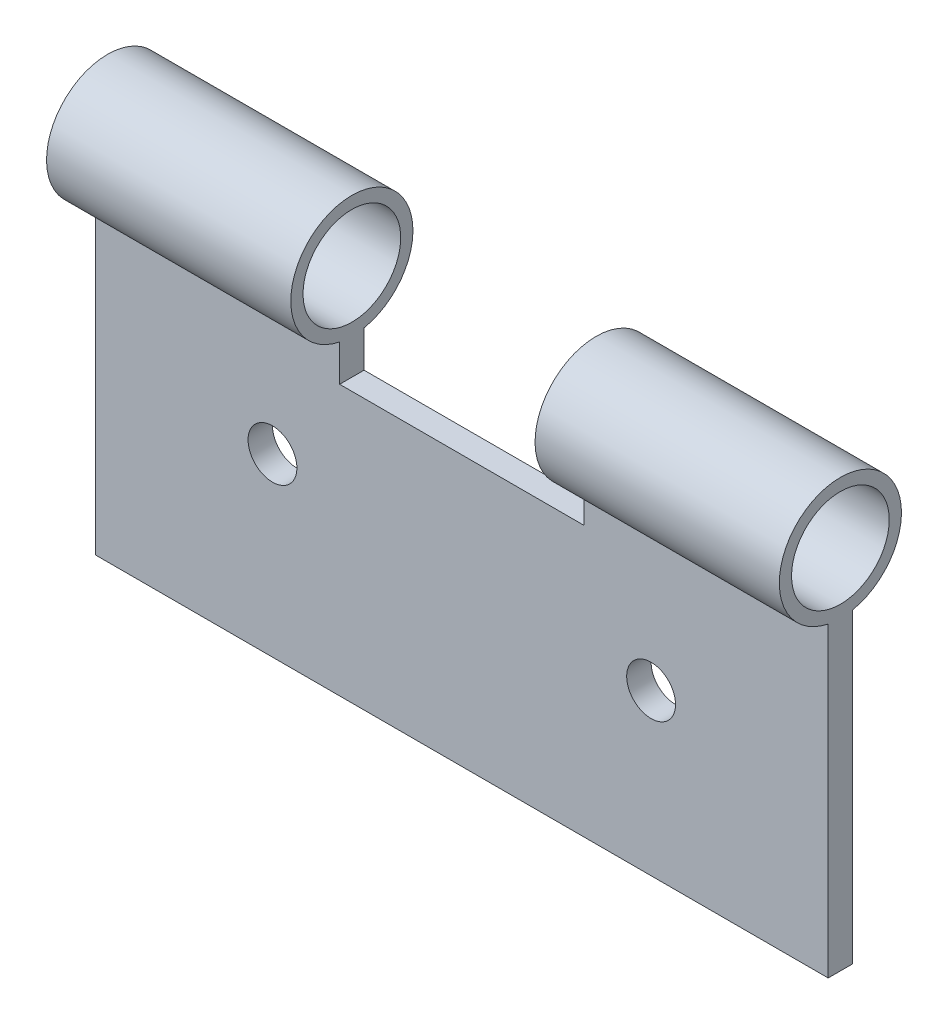
SolidWorks part; units mm, degrees
ref_plane "前视基准面" through (0, 0, 0) normal (0, 0, 1) x (1, 0, 0)
ref_plane "上视基准面" through (0, 0, 0) normal (0, 1, 0) x (1, 0, 0)
ref_plane "右视基准面" through (0, 0, 0) normal (1, 0, 0) x (0, 0, -1)
sketch "草图2" plane through (0, 0, 0) normal (1, 0, 0) x (0, 0, -1)
  line L0 (-0.0335, 0.5023) -> (0.05, -0.75) construction
  line L2 (-0.05, 0.5051) -> (-0.05, -0.75)
  line L3 (-0.05, -0.75) -> (0.05, -0.75)
  line L4 (0.05, 0.5051) -> (0.05, -0.75)
  line L6 (-0.05, -0.75) -> (0.0335, 0.5023) construction
  arc A0 (0.05, 0.5051) -> (-0.05, 0.5051) centre (0, 0.75) ccw
  circle A1 centre (0, 0.75) radius 0.2
  point P0 (0, 0)
  dimension "D1" = 0.1
extrude "凸台-拉伸1" add sketch "草图2" along normal blind 3
sketch "草图3" plane through (0, 0, -0.05) normal (0, 0, -1) x (-1, 0, 0)
  line L0 (-3, -0.1225) -> (0, 0)
  line L1 (-3, -0.75) -> (-3, 0.5051) construction
  circle A0 centre (-0.725, -0.0296) radius 0.1
  circle A1 centre (-2.275, -0.0929) radius 0.1
  dimension "D3" = 0.2
  dimension "D4" = 0.2
  dimension "D1" = 0.725
  dimension "D2" = 0.725
extrude "切除-拉伸1" cut sketch "草图3" against normal blind 3 contours L0 A1 | L0 A1 | L0 A0 | L0 A0 region at (2.2767, -0.0505, -0.05) region at (0.7267, 0.0128, -0.05) region at (0.7233, -0.072, -0.05) region at (2.2733, -0.1353, -0.05)
sketch "草图4" plane through (0, 0, 0.05) normal (0, 0, 1) x (1, 0, 0)
  line L0 (3, 0.5051) -> (0, 0.5051) construction
  line L1 (1, -0.7032) -> (2, -0.7032)
  line L2 (1, -0.7032) -> (1, 1.7133)
  line L3 (1, 1.7133) -> (2, 1.7133)
  line L4 (2, -0.7032) -> (2, 1.7133)
  line L5 (1, -0.7032) -> (2, 1.7133) construction
  line L6 (1, 1.7133) -> (2, -0.7032) construction
  line L7 (2, 0.3551) -> (1, 0.3551)
  point P0 (1.5, 0.5051)
  line M6 (3, 0.5051) -> (0, 0.5051)
  dimension "D1" = 1
  dimension "D2" = 0.15
extrude "切除-拉伸2" cut sketch "草图4" against normal blind 3 and the other way blind 3 contours L4 L3 L2 M6 | L7 L4 L2 M6 region at (1.5, 0.4301, 0.05) region at (1.5, 1.1092, 0.05)
